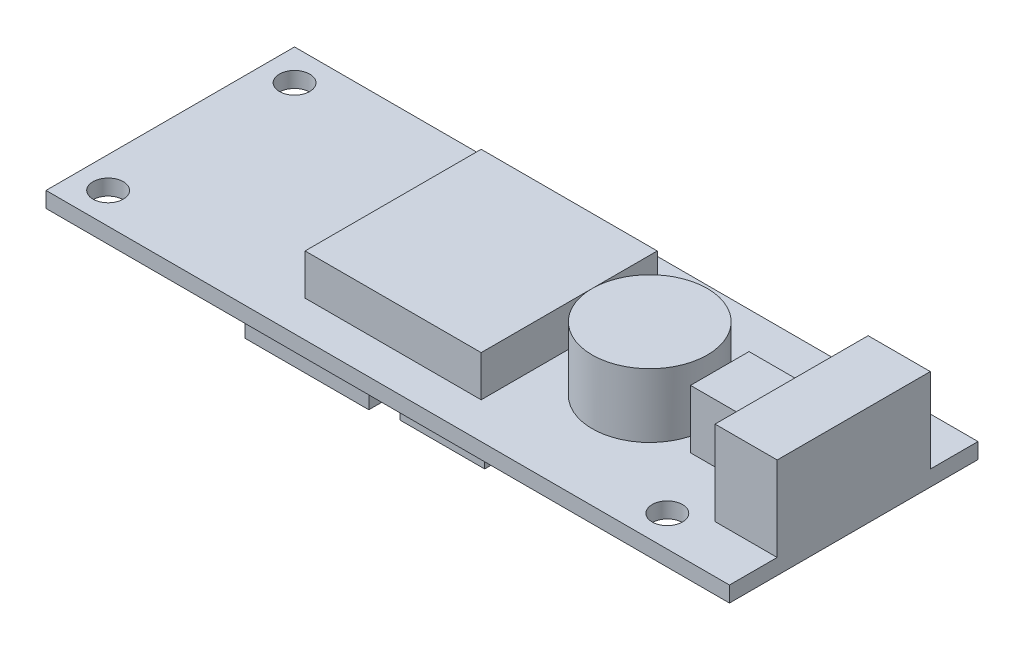
SolidWorks part; units mm, degrees
ref_plane "Front Plane" through (0, 0, 0) normal (0, 0, 1) x (1, 0, 0)
ref_plane "Top Plane" through (0, 0, 0) normal (0, 1, 0) x (1, 0, 0)
ref_plane "Right Plane" through (0, 0, 0) normal (1, 0, 0) x (0, 0, -1)
sketch "Sketch1" plane through (0, 0, 0) normal (0, 1, 0) x (1, 0, 0)
  line L1 (-34.925, -12.7) -> (34.925, -12.7)
  line L2 (-34.925, -12.7) -> (-34.925, 12.7)
  line L3 (-34.925, 12.7) -> (34.925, 12.7)
  line L4 (34.925, -12.7) -> (34.925, 12.7)
  line L5 (-34.925, -12.7) -> (34.925, 12.7) construction
  line L6 (-34.925, 12.7) -> (34.925, -12.7) construction
  circle A0 centre (-31.75, 9.525) radius 1.5494
  circle A1 centre (-31.75, -9.525) radius 1.5494
  circle A4 centre (25.4, 9.525) radius 1.5494
  circle A5 centre (25.4, -9.525) radius 1.5494
  point P0 (0, 0)
  point P6 (0, 0)
  point P8 (0, 0)
  point P9 (0, 0)
  point P15 (0, 0)
  point P16 (0, 0)
  point P17 (0, 0)
  point P18 (0, 0)
  dimension "D5" = 3.0988
  dimension "D1" = 25.4
  dimension "D2" = 69.85
  dimension "D3" = 9.525
  dimension "D4" = 3.175
  dimension "D6" = 3.175
  dimension "D7" = 3.175
extrude "PCB" add sketch "Sketch1" along normal blind 1.6
sketch "top_features" plane through (0, 1.6, 0) normal (0, 1, 0) x (1, 0, 0)
  line L0 (-34.925, 0) -> (34.925, 0) construction
  line L1 (28.5725, 7.8245) -> (34.925, 7.8245)
  line L2 (28.5725, 7.8245) -> (28.5725, -7.8245)
  line L3 (28.5725, -7.8245) -> (34.925, -7.8245)
  line L4 (34.925, 7.8245) -> (34.925, -7.8245)
  line L5 (21.2344, 2.9908) -> (25.9744, 2.9908)
  line L6 (21.2344, 2.9908) -> (21.2344, -2.9908)
  line L7 (21.2344, -2.9908) -> (25.9744, -2.9908)
  line L8 (25.9744, 2.9908) -> (25.9744, -2.9908)
  line L9 (-12.1488, 8.9979) -> (5.8471, 8.9979)
  line L10 (-12.1488, 8.9979) -> (-12.1488, -8.9979)
  line L11 (-12.1488, -8.9979) -> (5.8471, -8.9979)
  line L12 (5.8471, 8.9979) -> (5.8471, -8.9979)
  line L13 (-34.925, 12.7) -> (-34.925, -12.7) construction
  line L14 (34.925, -12.7) -> (34.925, 12.7) construction
  line L16 (8.195, 0) -> (8.195, 50000) construction
  circle A0 centre (14.08, 0) radius 5.885
  point P18 (34.925, 0)
  point P19 (25.9744, 0)
  point P20 (5.8471, 0)
  dimension "D9" = 11.77
  dimension "D1" = 5.9817
  dimension "D2" = 15.6489
  dimension "D3" = 17.9959
  dimension "D4" = 17.9959
  dimension "D5" = 4.74
  dimension "D6" = 22.7762
  dimension "D7" = 56.1594
  dimension "D8" = 6.3525
  dimension "D10" = 43.12
sketch "bottom_features" plane through (0, 0, 0) normal (0, -1, 0) x (1, 0, 0)
  line L0 (34.925, -12.7) -> (-34.925, -12.7) construction
  line L1 (-21.125, 0.4838) -> (-16.1212, 0.4838)
  line L2 (-21.125, 0.4838) -> (-21.125, -4.52)
  line L3 (-21.125, -4.52) -> (-16.1212, -4.52)
  line L4 (-16.1212, 0.4838) -> (-16.1212, -4.52)
  line L5 (-15.765, 11.54) -> (-3.0904, 11.54)
  line L6 (-15.765, 11.54) -> (-15.765, 0.9482)
  line L7 (-15.765, 0.9482) -> (-3.0904, 0.9482)
  line L8 (-3.0904, 11.54) -> (-3.0904, 0.9482)
  line L9 (-13.9717, -5.7528) -> (-8.945, -5.7528)
  line L10 (-13.9717, -5.7528) -> (-13.9717, -8.75)
  line L11 (-13.9717, -8.75) -> (-8.945, -8.75)
  line L12 (-8.945, -5.7528) -> (-8.945, -8.75)
  line L13 (0.429, 11.86) -> (9.065, 11.86)
  line L14 (0.429, 11.86) -> (0.429, 6.5895)
  line L15 (0.429, 6.5895) -> (9.065, 6.5895)
  line L16 (9.065, 11.86) -> (9.065, 6.5895)
  line L17 (2.1927, 2.9223) -> (9.165, 2.9223)
  line L18 (2.1927, 2.9223) -> (2.1927, -4.05)
  line L19 (2.1927, -4.05) -> (9.165, -4.05)
  line L20 (9.165, 2.9223) -> (9.165, -4.05)
  line L21 (11.3759, -6.8707) -> (19.415, -6.8707)
  line L22 (11.3759, -6.8707) -> (11.3759, -12.7)
  line L23 (11.3759, -12.7) -> (19.415, -12.7)
  line L24 (19.415, -6.8707) -> (19.415, -12.7)
  line L25 (-34.925, -12.7) -> (-34.925, 12.7) construction
  line L26 (-34.925, 12.7) -> (34.925, 12.7) construction
  line L27 (34.925, 12.7) -> (34.925, -12.7) construction
  line L28 (34.925, -7.8245) -> (34.925, 7.8245) construction
  line L29 (31.315, 6.4) -> (31.315, -6.4) construction
  line L30 (11.175, 9.36) -> (16.215, 9.36)
  line L31 (11.175, 9.36) -> (11.175, 6.34)
  line L32 (11.175, 6.34) -> (16.215, 6.34)
  line L33 (16.215, 9.36) -> (16.215, 6.34)
  line L34 (32.175, 6.4) -> (32.175, -6.4)
  line L35 (30.455, 6.4) -> (30.455, -6.4)
  line L36 (32.0875, 7.26) -> (50032.0875, 7.26) construction
  line L37 (32.0875, -7.26) -> (50032.0875, -7.26) construction
  line L39 (-34.925, 0) -> (34.925, 0) construction
  line L41 (25.765, 2.01) -> (29.015, 2.01)
  line L42 (25.765, 2.01) -> (25.765, 0.34)
  line L43 (25.765, 0.34) -> (29.015, 0.34)
  line L44 (29.015, 2.01) -> (29.015, 0.34)
  arc A0 (32.175, 6.4) -> (30.455, 6.4) centre (31.315, 6.4) ccw
  arc A1 (30.455, -6.4) -> (32.175, -6.4) centre (31.315, -6.4) ccw
  point P40 (31.315, 0)
  point P47 (31.315, 7.26)
  point P50 (31.315, -7.26)
  dimension "D1" = 5.0038
  dimension "D2" = 10.5918
  dimension "D3" = 12.6746
  dimension "D4" = 5.0267
  dimension "D5" = 2.9972
  dimension "D6" = 5.2705
  dimension "D7" = 8.636
  dimension "D8" = 8.0391
  dimension "D9" = 5.8293
  dimension "D10" = 6.9723
  dimension "D11" = 8.18
  dimension "D12" = 13.8
  dimension "D13" = 19.16
  dimension "D14" = 1.16
  dimension "D15" = 0.84
  dimension "D16" = 25.86
  dimension "D17" = 8.65
  dimension "D18" = 25.76
  dimension "D19" = 15.51
  dimension "D20" = 25.98
  dimension "D21" = 3.95
  dimension "D22" = 5.04
  dimension "D23" = 3.02
  dimension "D24" = 3.34
  dimension "D25" = 18.71
  dimension "D26" = 1.72
  dimension "D27" = 14.52
  dimension "D28" = 2.75
  dimension "D29" = 1.67
  dimension "D30" = 3.25
  dimension "D31" = 5.91
  dimension "D32" = 13.04
extrude "gps_antenna" add sketch "top_features" along normal blind 4.18 contours L9 L12 L11 L10
extrude "jst_connector" add sketch "Sketch2<3>" along normal blind 5.97 contours L7 L8 L5 L6
sketch "Sketch2<3>" plane through (0, 1.6, 0) normal (0, 1, 0) x (1, 0, 0) same geometry as "top_features"
extrude "terminal_block" add sketch "Sketch2<4>" along normal blind 8.63 contours L3 L4 L1 L2
sketch "Sketch2<4>" plane through (0, 1.6, 0) normal (0, 1, 0) x (1, 0, 0) same geometry as "top_features"
extrude "cc1200" add sketch "bottom_features" along normal blind 1.13 contours L2 L3 L4 L1
extrude "ublox" add sketch "bottom_features<4>" along normal blind 2.48 contours L6 L7 L8 L5
sketch "bottom_features<4>" plane through (0, 0, 0) normal (0, -1, 0) x (1, 0, 0) same geometry as "bottom_features"
extrude "flash" add sketch "bottom_features<5>" along normal blind 1.48 contours L14 L15 L16 L13
sketch "bottom_features<5>" plane through (0, 0, 0) normal (0, -1, 0) x (1, 0, 0) same geometry as "bottom_features"
extrude "baro" add sketch "bottom_features<6>" along normal blind 1.22 contours L32 L33 L30 L31
sketch "bottom_features<6>" plane through (0, 0, 0) normal (0, -1, 0) x (1, 0, 0) same geometry as "bottom_features"
extrude "uC" add sketch "bottom_features<7>" along normal blind 0.87 contours L20 L19 L18 L17
sketch "bottom_features<7>" plane through (0, 0, 0) normal (0, -1, 0) x (1, 0, 0) same geometry as "bottom_features"
extrude "usb" add sketch "bottom_features<8>" along normal blind 2.57 contours L22 L23 L24 L21
sketch "bottom_features<8>" plane through (0, 0, 0) normal (0, -1, 0) x (1, 0, 0) same geometry as "bottom_features"
extrude "accelerometer" add sketch "bottom_features<9>" along normal blind 1.12 contours L11 L12 L9 L10
sketch "bottom_features<9>" plane through (0, 0, 0) normal (0, -1, 0) x (1, 0, 0) same geometry as "bottom_features"
extrude "terminalblock_solder" add sketch "bottom_features<10>" along normal blind 2.17 contours L34 A1 L35 A0
sketch "bottom_features<10>" plane through (0, 0, 0) normal (0, -1, 0) x (1, 0, 0) same geometry as "bottom_features"
extrude "Boss-Extrude13" add sketch "top_features<5>" along normal blind 6.53 contours A0 region at (14.08, 1.6, 0)
sketch "top_features<5>" plane through (0, 1.6, 0) normal (0, 1, 0) x (1, 0, 0) same geometry as "top_features"
